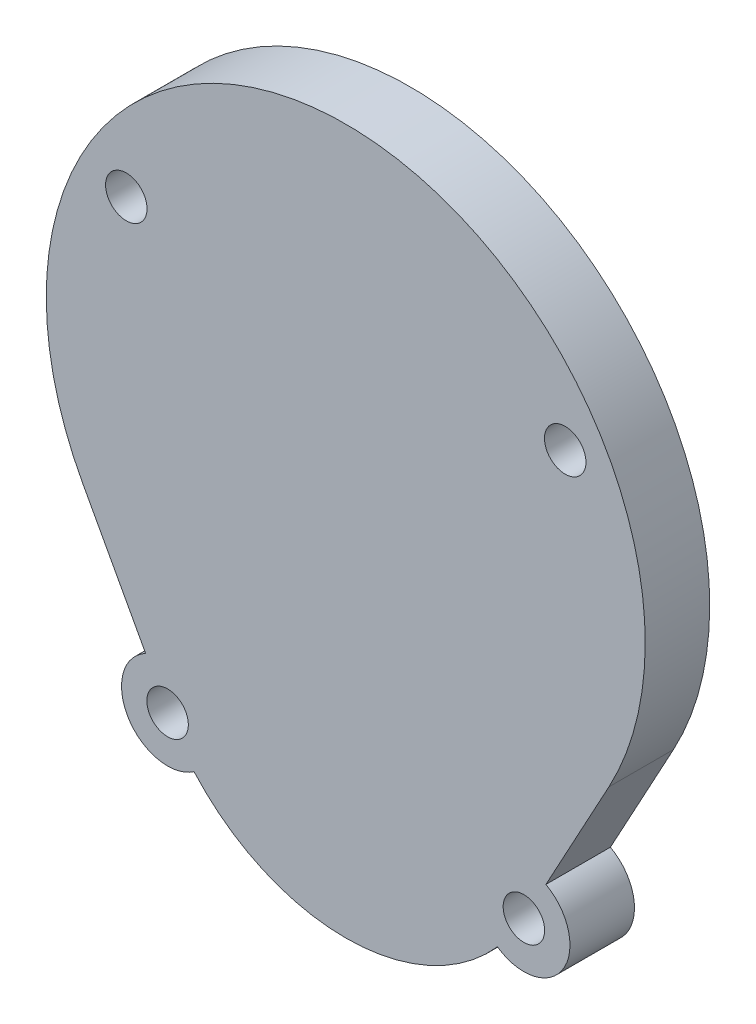
SolidWorks part; units mm, degrees
material "PET"
ref_plane "Front Plane" through (0, 0, 0) normal (0, 0, 1) x (1, 0, 0)
ref_plane "Top Plane" through (0, 0, 0) normal (0, 1, 0) x (1, 0, 0)
ref_plane "Right Plane" through (0, 0, 0) normal (1, 0, 0) x (0, 0, -1)
sketch "Sketch1" plane through (0, 0, 0) normal (0, 0, 1) x (1, 0, 0)
  line L0 (-28.5595, -15.5114) -> (-21.719, -28.1062)
  line L1 (28.5595, -15.5114) -> (21.719, -28.1062)
  line L2 (0, 0) -> (0, -22) construction
  line L3 (0, -22) -> (0, -44) construction
  line L6 (-23.8157, 13.75) -> (0, 0) construction
  line L7 (0, 0) -> (23.8157, 13.75) construction
  line L10 (-21.719, -28.1062) -> (-19.3326, -32.5) construction
  line L11 (21.719, -28.1062) -> (19.3326, -32.5) construction
  arc A0 (28.5595, -15.5114) -> (-28.5595, -15.5114) centre (0, 0) ccw
  arc A1 (-16.4624, -36.5941) -> (16.4624, -36.5941) centre (0, -22) ccw
  circle A5 centre (-23.8157, 13.75) radius 2.25
  circle A6 centre (23.8157, 13.75) radius 2.25
  arc A7 (-21.719, -28.1062) -> (-16.4624, -36.5941) centre (-19.3326, -32.5) ccw
  arc A8 (16.4624, -36.5941) -> (21.719, -28.1062) centre (19.3326, -32.5) ccw
  arc A9 (-19.3326, -32.5) -> (19.3326, -32.5) centre (0, -22) ccw construction
  circle A10 centre (-19.3326, -32.5) radius 2.25
  circle A11 centre (19.3326, -32.5) radius 2.25
  dimension "D1" = 65
  dimension "D2" = 22
  dimension "D3" = 44
  dimension "D4" = 10
  dimension "D5" = 4.5
  dimension "D6" = 4.5
  dimension "D7" = 10
  dimension "D10" = 5
  dimension "D11" = 5
  dimension "D12" = 4.5
  dimension "D13" = 4.5
  dimension "D8" = 120
  dimension "D9" = 120
extrude "Boss-Extrude1" add sketch "Sketch1" along normal blind 7
sketch "Sketch2" plane through (0, 0, 0) normal (0, 0, -1) x (-1, 0, 0)
  line L0 (-28.5595, -15.5114) -> (-19.3326, -32.5) construction
  line L3 (19.3326, -32.5) -> (28.5595, -15.5114) construction
  line L4 (-23.7264, -12.8864) -> (-14.4995, -29.875)
  line L7 (14.4995, -29.875) -> (23.7264, -12.8864)
  line L8 (-21.0901, -11.4545) -> (-11.8632, -28.4432)
  line L9 (-21.719, -28.1062) -> (-28.5595, -15.5114) construction
  line L10 (28.5595, -15.5114) -> (21.719, -28.1062) construction
  line L11 (11.8632, -28.4432) -> (21.0901, -11.4545)
  line L12 (-10.332, -34.8647) -> (1.0028, -47.1659) construction
  line L13 (4.4391, -48.3739) -> (14.4951, -29.883) construction
  line L14 (-8.2859, -32.6581) -> (2.9434, -44.8447) construction
  line L15 (2.9434, -44.8447) -> (11.8596, -28.4497) construction
  line L16 (-14.1176, -38.8729) -> (-3.0691, -50.8634) construction
  line L17 (8.3178, -52.7538) -> (19.3268, -32.5107) construction
  arc A0 (28.5595, -15.5114) -> (-28.5595, -15.5114) centre (0, 0) ccw construction
  arc A4 (23.7264, -12.8864) -> (24.327, 11.7132) centre (0, 0) ccw
  arc A6 (-14.4995, -29.875) -> (14.4995, -29.875) centre (0, -22) ccw
  arc A8 (21.0901, -11.4545) -> (-21.0901, -11.4545) centre (0, 0) ccw
  arc A10 (-11.8632, -28.4432) -> (-8.2859, -32.6581) centre (0, -22) ccw construction
  arc A12 (-24.327, 11.7132) -> (-22.3074, 15.2112) centre (-23.8157, 13.75) ccw
  arc A13 (22.3074, 15.2112) -> (24.327, 11.7132) centre (23.8157, 13.75) ccw
  arc A15 (-24.327, 11.7132) -> (-23.7264, -12.8864) centre (0, 0) ccw
  arc A16 (23.7264, -12.8864) -> (-23.7264, -12.8864) centre (0, 0) ccw construction
  arc A17 (22.3074, 15.2112) -> (-22.3074, 15.2112) centre (0, 0) ccw
  arc A18 (2.9434, -44.8447) -> (2.9434, -44.8447) centre (2.9434, -44.8447) ccw construction
  arc A19 (-14.4995, -29.875) -> (-10.332, -34.8647) centre (0, -22) ccw construction
  arc A20 (-19.3326, -32.5) -> (-14.1176, -38.8729) centre (0, -22) ccw construction
  arc A21 (-3.0691, -50.8634) -> (8.3178, -52.7538) centre (3.8084, -44.6764) ccw construction
  arc A22 (19.3268, -32.5107) -> (19.3326, -32.5) centre (0, -22) ccw construction
  circle A23 centre (0, -22) radius 22 construction
  arc A24 (-16.4624, -36.5941) -> (16.4624, -36.5941) centre (0, -22) ccw construction
  arc A25 (14.4951, -29.883) -> (14.4995, -29.875) centre (0, -22) ccw construction
  arc A26 (11.8596, -28.4497) -> (11.8632, -28.4432) centre (0, -22) ccw construction
  arc A27 (1.0028, -47.1659) -> (4.4391, -48.3739) centre (3.8084, -44.6764) ccw construction
  arc A28 (-11.8632, -28.4432) -> (11.8632, -28.4432) centre (0, -22) ccw
  circle M19 centre (23.8157, 13.75) radius 2.25
  circle M20 centre (-23.8157, 13.75) radius 2.25
  dimension "D3" = 4.2
  dimension "D5" = 4.2
  dimension "D1" = 5.5
  dimension "D2" = 3
extrude "Boss-Extrude2" add sketch "Sketch2" along normal blind 2 contours A17 A15 L4 L7 A4 L8 A8 L11 M19 M20 region at (26.1414, -0.7123, 0)
sketch "Sketch3" plane through (0, 0, 0) normal (0, 0, -1) x (-1, 0, 0)
  circle A0 centre (0, -22) radius 7.05
  dimension "D1" = 14.1
extrude "Cut-Extrude1" cut sketch "Sketch3" against normal blind 5
sketch "Sketch4" plane through (0, 0, 0) normal (0, 0, -1) x (-1, 0, 0)
  circle A0 centre (0, 0) radius 7.5
  dimension "D1" = 15
extrude "Cut-Extrude2" cut sketch "Sketch4" against normal blind 2
sketch "Sketch5" plane through (0, 0, 0) normal (0, 0, -1) x (-1, 0, 0)
  line L0 (-17.9379, -17.2585) -> (-21.0901, -11.4545)
  line L1 (17.9379, -17.2585) -> (21.0901, -11.4545)
  arc A0 (12.5195, -16.9491) -> (-12.5195, -16.9491) centre (0, -22) ccw
  arc A3 (-11.8632, -28.4432) -> (11.8632, -28.4432) centre (0, -22) ccw construction
  arc A4 (21.0901, -11.4545) -> (-21.0901, -11.4545) centre (0, 0) ccw
  arc A5 (-17.9379, -17.2585) -> (-12.5195, -16.9491) centre (-15.3016, -15.8266) ccw
  arc A6 (17.9379, -17.2585) -> (12.5195, -16.9491) centre (15.3016, -15.8266) cw
  point P14 (-11.8632, -28.4432)
  point P20 (11.8632, -28.4432)
  dimension "D1" = 3
  dimension "D2" = 3
extrude "Cut-Extrude3" cut sketch "Sketch5" against normal blind 4
